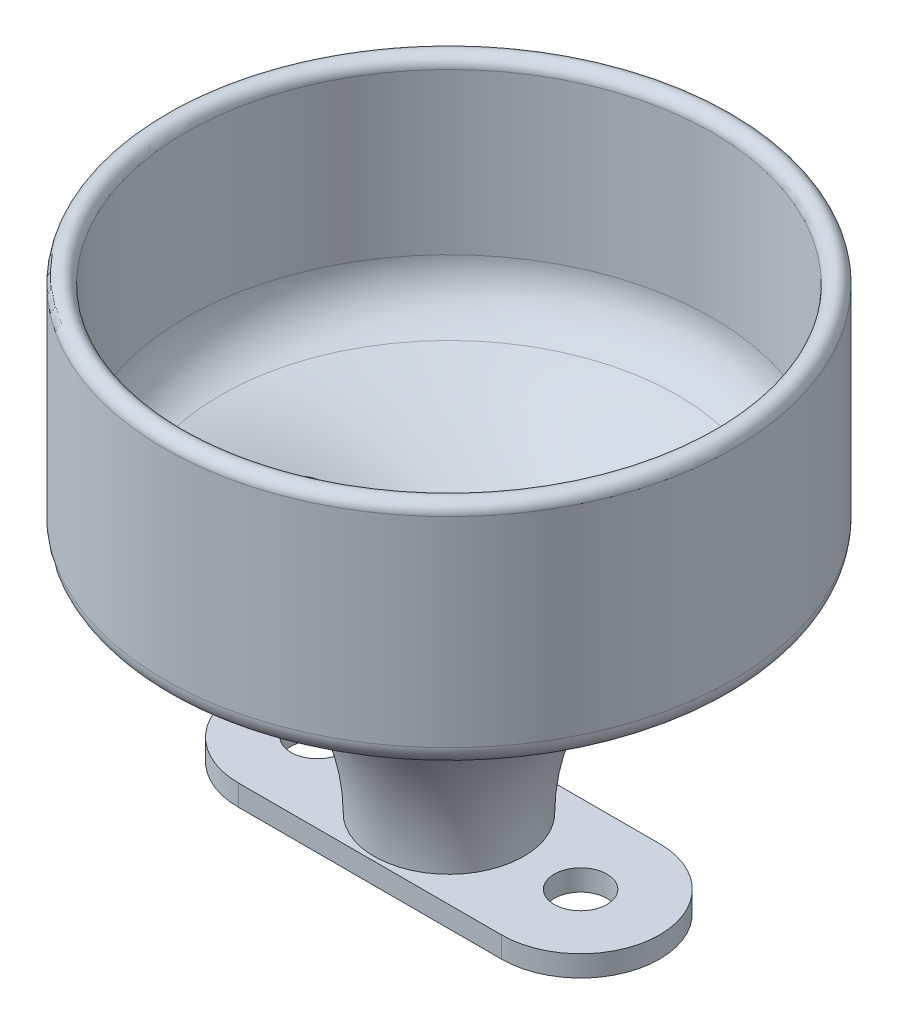
SolidWorks part; units mm, degrees
ref_plane "Front Plane" through (0, 0, 0) normal (0, 0, 1) x (1, 0, 0)
ref_plane "Top Plane" through (0, 0, 0) normal (0, 1, 0) x (1, 0, 0)
ref_plane "Right Plane" through (0, 0, 0) normal (1, 0, 0) x (0, 0, -1)
sketch "Sketch1" plane through (0, 0, 0) normal (0, 0, 1) x (1, 0, 0)
  line L0 (-3.2385, 0) -> (-12.7, 0)
  line L1 (-12.7, 0) -> (-12.7, 1.27)
  line L2 (-12.7, 1.27) -> (-4.5085, 1.27)
  line L3 (0, 0) -> (0, 29.5112) construction
  line L4 (-3.2385, 0) -> (-3.2385, 1.27)
  line L5 (-4.5085, 1.27) -> (-3.2385, 1.27) construction
  line L6 (-6.35, 1.27) -> (-6.35, 0) construction
  line L7 (-15.875, 29.5112) -> (0, 29.5112) construction
  line L9 (-17.145, 16.8112) -> (-17.145, 29.5112)
  line L10 (-17.145, 29.5112) -> (-15.875, 29.5112)
  line L11 (-15.875, 16.8112) -> (-15.875, 29.5112)
  arc A0 (-4.5085, 1.27) -> (-16.1341, 15.5679) centre (-19.1135, 1.27) ccw
  arc A1 (-3.2385, 1.27) -> (-15.875, 16.8112) centre (-19.1135, 1.27) ccw
  arc A2 (-16.1341, 15.5679) -> (-17.145, 16.8112) centre (-15.875, 16.8112) cw
  point P10 (0, 0)
  point P11 (-17.3315, 15.7382)
  point P18 (0, 0)
  point P19 (-17.1859, 28.8923)
  dimension "D5" = 31.75
  dimension "D6" = 15.875
  dimension "D1" = 1.27
  dimension "D2" = 6.477
  dimension "D3" = 6.35
  dimension "D4" = 12.7
  dimension "D7" = 12.7
revolve "Revolve1" add sketch "Sketch1" angle 360 about L3
fillet "Fillet1" 2 edges at (0, 29.5112, -17.145) (0, 29.5112, -15.875) type full round first side face at (0, 16.8112, -17.145) second side face at (0, 29.5112, -15.875) middle face at (0, 29.5112, -17.145)
fillet "Fillet2" radius 3.175 1 edges at (0, 16.8112, -15.875)
sketch "Sketch2" plane through (0, 0, 0) normal (0, -1, 0) x (1, 0, 0)
  line L0 (-7.9375, 0) -> (7.9375, 0) construction
  circle A0 centre (-7.9375, 0) radius 1.5875
  circle A1 centre (7.9375, 0) radius 1.5875
  point P4 (0, 0)
  dimension "D1" = 3.175
  dimension "D2" = 15.875
extrude "Cut-Extrude1" cut sketch "Sketch2" against normal through all both and the other way through all
sketch "Sketch3" plane through (0, 0, 0) normal (0, -1, 0) x (-1, 0, 0)
  line L0 (7.9375, 0) -> (-7.9375, 0) construction
  line L1 (7.9375, -4.7625) -> (-7.9375, -4.7625)
  line L2 (7.9375, 4.7625) -> (-7.9375, 4.7625)
  arc A0 (7.9375, -4.7625) -> (7.9375, 4.7625) centre (7.9375, 0) ccw
  arc A1 (-7.9375, 4.7625) -> (-7.9375, -4.7625) centre (-7.9375, 0) ccw
  circle A3 centre (0, 0) radius 12.7 construction
  point P4 (0, 0)
extrude "Cut-Extrude2" cut sketch "Sketch3" against normal blind 2.54 flip side to cut
